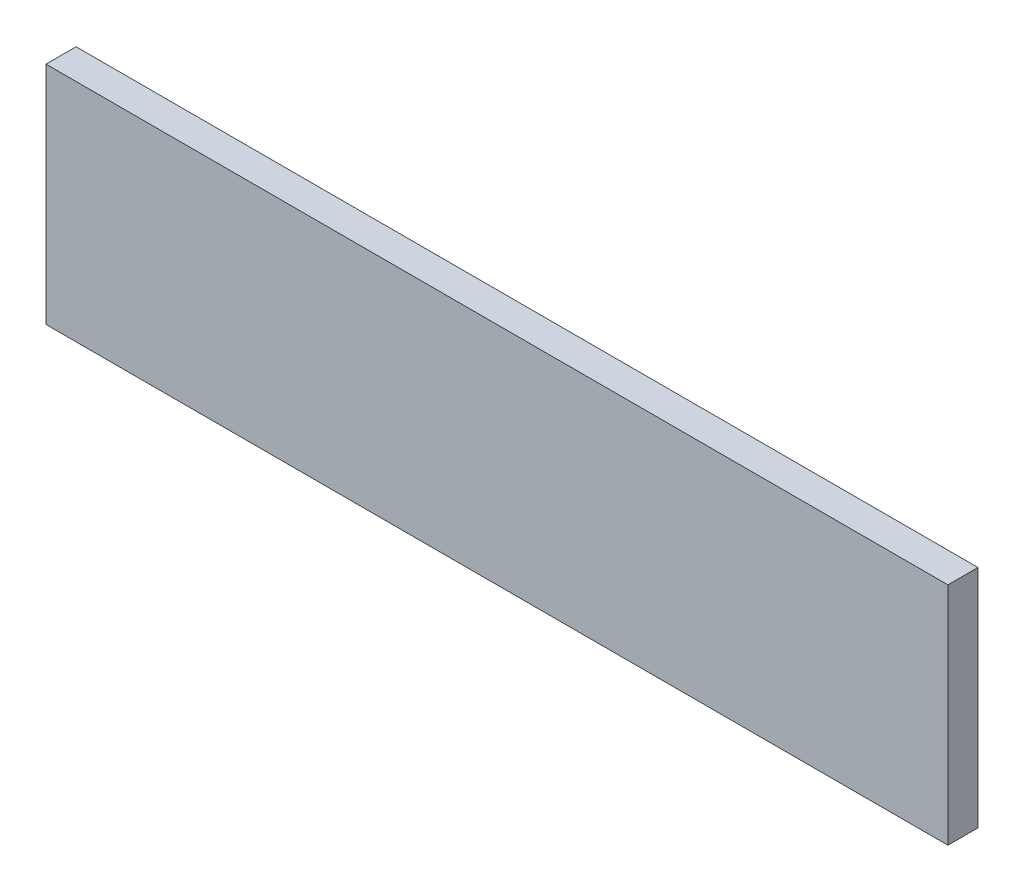
SolidWorks part; units mm, degrees
ref_plane "Ebene vorne" through (0, 0, 0) normal (0, 0, 1) x (1, 0, 0)
ref_plane "Ebene oben" through (0, 0, 0) normal (0, 1, 0) x (1, 0, 0)
ref_plane "Ebene rechts" through (0, 0, 0) normal (1, 0, 0) x (0, 0, -1)
sketch "Skizze1" plane through (0, 0, 0) normal (0, 0, 1) x (1, 0, 0)
  line L0 (-150, -75) -> (-150, 55) construction
  line L1 (150, -150) -> (-150, -150)
  line L2 (150, -150) -> (150, -75)
  line L3 (150, -75) -> (-150, -75)
  line L4 (-150, -150) -> (-150, -75)
  dimension "D1" = 75
extrude "Linear austragen1" add sketch "Skizze1" along normal blind 10
